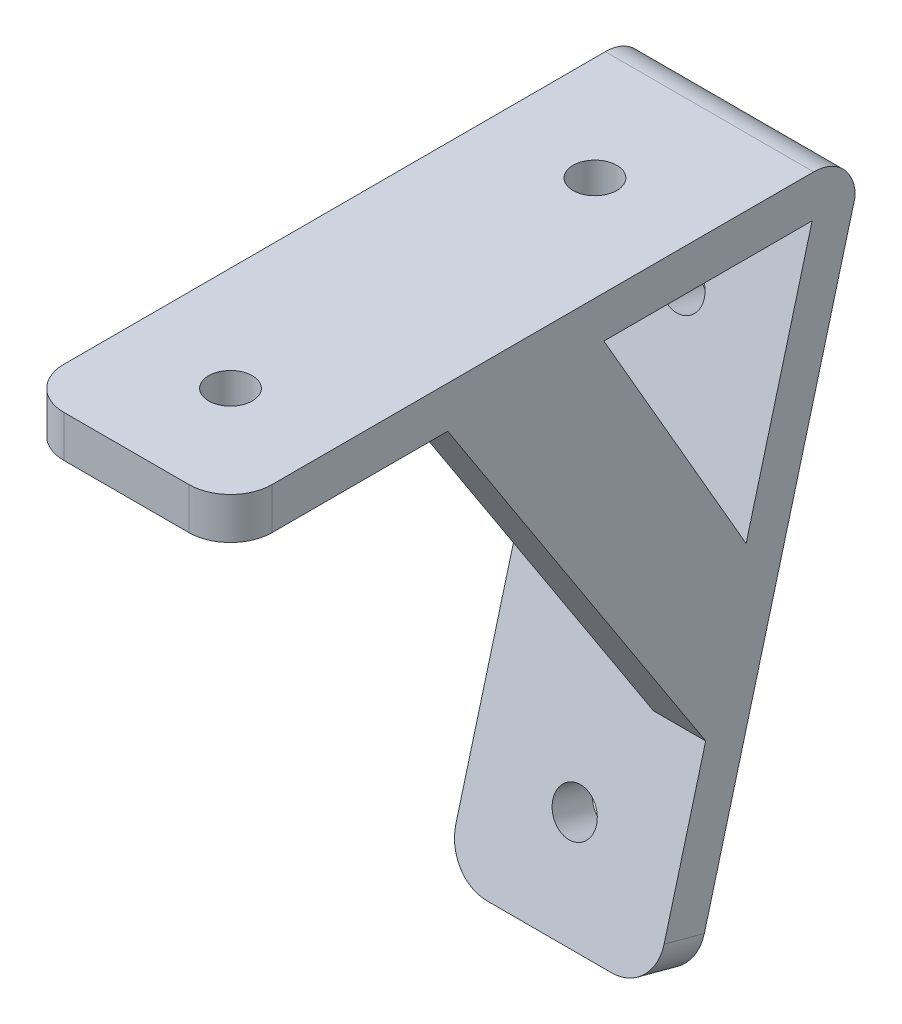
SolidWorks part; units mm, degrees
ref_plane "Front Plane" through (0, 0, 0) normal (0, 0, 1) x (1, 0, 0)
ref_plane "Top Plane" through (0, 0, 0) normal (0, 1, 0) x (1, 0, 0)
ref_plane "Right Plane" through (0, 0, 0) normal (1, 0, 0) x (0, 0, -1)
sketch "Sketch1" plane through (0, 0, 0) normal (0, 1, 0) x (1, 0, 0)
  line L1 (10, -30) -> (-10, -30)
  line L2 (10, -30) -> (10, 30)
  line L3 (10, 30) -> (-10, 30)
  line L4 (-10, -30) -> (-10, 30)
  line L5 (10, -30) -> (-10, 30) construction
  line L6 (10, 30) -> (-10, -30) construction
  point P0 (0, 0)
  dimension "D1" = 20
  dimension "D2" = 60
extrude "Boss-Extrude1" add sketch "Sketch1" along normal blind 4
ref_plane "Plane1" through (0, -7.5, -27.9904) normal (0, -0.2588, -0.9659) x (-1, 0, 0)
sketch "Sketch6" plane through (0, -7.5, -27.9904) normal (0, -0.2588, -0.9659) x (-1, 0, 0)
  line L1 (10, 7.7646) -> (-10, 7.7646)
  line L2 (10, 7.7646) -> (10, -52.2354)
  line L3 (10, -52.2354) -> (-10, -52.2354)
  line L4 (-10, 7.7646) -> (-10, -52.2354)
  dimension "D1" = 60
extrude "Boss-Extrude3" add sketch "Sketch6" against normal blind 4
fillet "Fillet6" radius 4 3 edges at (0, 4, -30) (-10, 2, -30) (10, 2, -30)
sketch "Sketch7" plane through (0, 0, 0) normal (0, -1, 0) x (1, 0, 0)
  circle A0 centre (0, 20) radius 2.1
  circle A1 centre (0, -15) radius 2.1
  dimension "D1" = 4.2
  dimension "D2" = 35
  dimension "D3" = 20
extrude "Cut-Extrude3" cut sketch "Sketch7" against normal blind 4
sketch "Sketch8" plane through (0, -6.4647, -24.1267) normal (0, 0.2588, 0.9659) x (1, 0, 0)
  line L0 (10, -22.7713) -> (-10, -22.7713) construction
  line L1 (10, 6.6928) -> (10, -52.2354) construction
  line L2 (-10, -52.2354) -> (-10, 6.6928) construction
  circle A0 centre (0, -2.7713) radius 2.1
  circle A1 centre (0, -42.7713) radius 2.1
  dimension "D1" = 4.2
  dimension "D2" = 40
  dimension "D3" = 20
  dimension "D4" = 10
extrude "Cut-Extrude4" cut sketch "Sketch8" against normal blind 4
fillet "Fillet7" radius 4 1 edges at (-10, -57.4379, -12.539)
fillet "Fillet8" radius 4 1 edges at (10, -57.4379, -12.539)
fillet "Fillet9" radius 4 1 edges at (10, 2, 30)
fillet "Fillet10" radius 4 1 edges at (-10, 2, 30)
sketch "Brace" plane through (10, 0, 0) normal (1, 0, 0) x (0, 0, -1)
  line L0 (15.6369, -38.1491) -> (-9.1411, 0)
  line L1 (25.8589, 0) -> (11.6424, -53.0566) construction
  line L2 (-26, 0) -> (25.8589, 0) construction
  line L3 (-9.1411, 0) -> (5.8589, 0)
  line L4 (5.8589, 0) -> (19.5191, -23.6603)
  line L5 (19.5191, -23.6603) -> (15.6369, -38.1491)
  dimension "D1" = 15
  dimension "D2" = 45
  dimension "D3" = 20
extrude "Boss-Extrude5" add sketch "Brace" against normal blind 5
